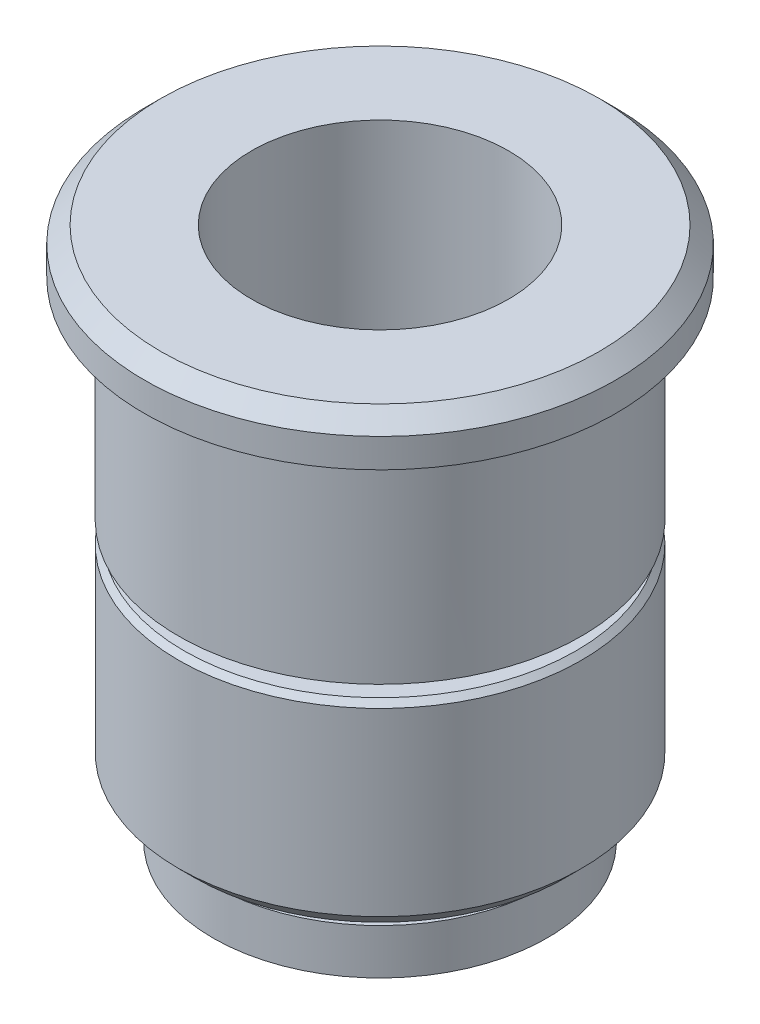
SolidWorks part; units mm, degrees
material "Brass"
ref_plane "Front" through (0, 0, 0) normal (0, 0, 1) x (1, 0, 0)
ref_plane "Top" through (0, 0, 0) normal (0, 1, 0) x (1, 0, 0)
ref_plane "Right" through (0, 0, 0) normal (1, 0, 0) x (0, 0, -1)
sketch "Sketch1" plane through (0, 0, 0) normal (0, 0, 1) x (1, 0, 0)
  line L0 (0, 0) -> (0, 6.23) construction
  line L1 (0, 0) -> (1.95, 0) construction
  line L2 (0, 6.23) -> (2.75, 6.23) construction
  line L3 (2.75, 6.23) -> (2.75, 5.7) construction
  line L4 (0, 0.71) -> (2.35, 0.71) construction
  line L5 (1.5, 6.23) -> (1.5, 0) construction
  line L6 (1.95, 0) -> (1.95, 0.53) construction
  line L7 (1.5, 0) -> (1.95, 0) construction
  line L8 (1.725, 0) -> (1.725, 6.23) construction
  line L9 (1.95, 0.53) -> (1.725, 0.53) construction
  line L10 (1.725, 0.53) -> (1.725, 0.71) construction
  line L11 (2.75, 5.7) -> (1.725, 5.7) construction
  line L12 (1.725, 5.7) -> (1.725, 5.61) construction
  line L13 (1.725, 5.61) -> (2.35, 5.61) construction
  line L14 (2.35, 5.61) -> (2.35, 3.25) construction
  line L15 (2.35, 3.25) -> (1.725, 3.25) construction
  line L16 (1.725, 3.25) -> (1.725, 3.07) construction
  line L17 (1.725, 3.07) -> (2.35, 3.07) construction
  line L18 (2.35, 3.07) -> (2.35, 0.71) construction
  line L19 (1.725, 0.71) -> (1.725, 0.53) construction
  point P13 (1.725, 0)
  point P15 (1.5, 5.73)
  dimension "BaseFlange" = 3.9
  dimension "FlangeDia" = 5.5
  dimension "Flange Thickness" = 0.53
  dimension "BodyDia" = 4.7
  dimension "ThreadDia" = 3
  dimension "D1" = 0.53
  dimension "D3" = 0.09
  dimension "D2" = 0.18
  dimension "D4" = 0.18
  dimension "Pitch" = 0.5
  dimension "knurled body ht" = 2.36
  dimension "Lg" = 5.7
sketch "Sketch3" plane through (0, 0, 0) normal (0, 0, 1) x (1, 0, 0)
  line L0 (0, 0) -> (1.95, 0)
  line L1 (1.95, 0) -> (1.95, 0.53)
  line L2 (1.95, 0.53) -> (1.725, 0.53)
  line L3 (1.725, 0.53) -> (1.725, 0.71)
  line L4 (1.725, 0.71) -> (2.35, 0.71)
  line L5 (2.35, 0.71) -> (2.35, 3.07)
  line L6 (2.35, 3.07) -> (1.725, 3.07)
  line L7 (1.725, 3.07) -> (1.725, 3.25)
  line L8 (1.725, 3.25) -> (2.35, 3.25)
  line L9 (2.35, 3.25) -> (2.35, 5.61)
  line L10 (2.35, 5.61) -> (1.725, 5.61)
  line L11 (1.725, 5.61) -> (1.725, 5.7)
  line L12 (1.725, 5.7) -> (2.75, 5.7)
  line L13 (2.75, 5.7) -> (2.75, 6.23)
  line L14 (2.75, 6.23) -> (0, 6.23)
  line L15 (0, 6.23) -> (0, 0)
revolve "Revolve1" add sketch "Sketch3" angle 360 about L0
sketch "Sketch5" plane through (0, 0, 0) normal (0, 0, 1) x (1, 0, 0)
  line L1 (0, 0) -> (1.5, 0)
  line L2 (0, 0) -> (0, 6.23)
  line L3 (0, 6.23) -> (1.5, 6.23)
  line L4 (1.5, 0) -> (1.5, 6.23)
revolve "Cut-Revolve1" cut sketch "Sketch5" angle 360 about L0
chamfer "Chamfer1" distance 0.0635 angle 45 2 edges at (0, 3.07, -2.35) (0, 5.61, -2.35)
chamfer "Chamfer2" distance 0.1925 angle 45 2 edges at (0, 6.23, -2.75) (0, 0.71, -2.35)
sketch "Sketch6" plane through (0, 6.23, 0) normal (0, 1, 0) x (1, 0, 0)
  circle A0 centre (0, 0) radius 1.5 construction
  circle A1 centre (0, 0) radius 1.5 construction
  circle A2 centre (0, 0) radius 1.5 construction
  circle A3 centre (0, 0) radius 1.5 construction
  circle A4 centre (0, 0) radius 1.5
curve "Helix/Spiral1" [suppressed] pitch 0.5 height 8.55 turns 17.1 parameters "Threa"=8.55, "Pitch"=0.5
sketch "Sketch13" plane through (0, 0, 0) normal (0, 0, 1) x (1, 0, 0)
  line L0 (-2.75, 5.7) -> (-2.75, 0) construction
  line L1 (-1.95, 0) -> (1.95, 0) construction
  line L2 (-2.75, 5.7) -> (2.75, 5.7) construction
  line L3 (-2.75, 6.0375) -> (-2.75, 5.7) construction
  line L4 (0, 0) -> (0, 6.23) construction
  line L5 (1.5, 6.23) -> (-1.5, 6.23) construction
  line L6 (0, 6.23) -> (1.5, 6.23) construction
  line L7 (-2.75, 5.7) -> (2.75, 5.7) construction
  line L8 (-2.75, 3.115) -> (2.75, 3.115) construction
  point P8 (1.5, 6.23)
  point P20 (0, 3.115)
sketch "Sketch14" plane through (0, 6.23, 0) normal (0, 1, 0) x (1, 0, 0)
  line L0 (0, 0) -> (1.0607, -1.0607) construction
  line L1 (0, 0) -> (0, -1.5) construction
  circle A0 centre (0, 0) radius 1.5 construction
  point P8 (1.0607, -1.0607)
  dimension "D1" = 45
sketch "Sketch7" [suppressed] plane through (0, 0, 0) normal (0, 0, 1) x (1, 0, 0)
  line L0 (-1.5, 6.23) -> (-1.5, 6.6675)
  line L1 (-1.5, 6.6675) -> (-1.1752, 6.48)
  line L2 (-1.1752, 6.48) -> (-1.1752, 6.4175)
  line L3 (-1.1752, 6.4175) -> (-1.5, 6.23)
  line L4 (-1.1752, 6.4488) -> (-1.5, 6.4488) construction
  line L5 (-1.3376, 6.5738) -> (-1.3376, 6.3238) construction
  dimension "D1" = 0.0625
  dimension "D2" = 0.25
  dimension "D3" = 60
sweep "Sweep1" [suppressed] add profiles "Sketch7" path "Helix/Spiral1"
sketch "Sketch9" [suppressed] plane through (0, 6.23, 0) normal (0, 1, 0) x (1, 0, 0)
  circle A0 centre (0, 0) radius 1.5 construction
  circle A1 centre (0, 0) radius 1.5
extrude "Cut-Extrude1" [suppressed] cut sketch "Sketch9" along normal blind 25.4 draft 45 and the other way blind 2.54 draft 45 draft outward yes
sketch "Sketch10" [suppressed] plane through (0, 0, 0) normal (0, -1, 0) x (1, 0, 0)
  circle A1 centre (0, 0) radius 1.5
  dimension "D1" = 3
extrude "Cut-Extrude2" [suppressed] cut sketch "Sketch10" along normal blind 25.908 draft 45 and the other way blind 6.35 draft 45 draft outward yes
sketch "Sketch11" [suppressed] plane through (0, 5.61, 0) normal (0, 1, 0) x (1, 0, 0)
  line L0 (0, 0) -> (0, -2.35) construction
  line L1 (0, 0) -> (0.1435, -2.3456) construction
  line L2 (0, 0) -> (-0.1435, -2.3456) construction
  circle A0 centre (0, 0) radius 2.35 construction
  circle A1 centre (0, -2.35) radius 0.1435
  dimension "D1" = 3.5
  dimension "D2" = 3.5
sketch "Sketch12" plane through (0, 5.61, 0) normal (0, 1, 0) x (1, 0, 0)
  circle A0 centre (0, 0) radius 2.35 construction
  circle A1 centre (0, 0) radius 2.35
curve "Helix/Spiral2" [suppressed] pitch 28.51 height 2.365 turns 0.083
sweep "Cut-Sweep1" [suppressed] cut profiles "Sketch11" path "Helix/Spiral2"
pattern_circular "CirPattern1" [suppressed] count 30 over 360 of bodies 117
ref_plane "Plane1" [suppressed] through (0, 3.16, 0) normal (0, -1, 0) x (-1, 0, 0)
mirror "Mirror1" [suppressed] about plane through (0, 3.16, 0) normal (0, -1, 0)
ref_plane "Contact Plane 1" [suppressed] through (0, 6.23, 0) normal (0, 1, 0) x (1, 0, 0)
ref_plane "Contact Plane 2" [suppressed] through (0, 0, 0) normal (0, 1, 0) x (1, 0, 0)
ref_plane "Contact Plane 3" [suppressed] through (-2.75, 0, 0) normal (1, 0, 0) x (0, 0, -1)
ref_plane "Contact Plane 4" [suppressed] through (2.75, 0, 0) normal (1, 0, 0) x (0, 0, -1)
ref_plane "Contact Plane 5" [suppressed] through (0, 3.115, 0) normal (0, 1, 0) x (1, 0, 0)
ref_plane "Contact Plane 6" [suppressed] through (0, 5.7, 0) normal (0, -1, 0) x (-1, 0, 0)
ref_axis "Center Axis 1" [suppressed] through (0, 7.0965, 0) along (0, -1, 0)
equation "\"D1@Sketch1\"=\"Flange Thickness@Sketch1\""
equation "\"D3@Sketch1\"=\"D2@Sketch1\"*.50"
equation "\"D4@Sketch1\"=\"D2@Sketch1\""
equation "\"Threa@Helix/Spiral1\" = \"Lg@Sketch1\" +  ( \"Lg@Sketch1\" / 2 ) "
equation "\"Pitch@Helix/Spiral1\"=\"Pitch@Sketch1\""
equation "\"D1@Sketch7\"=\"Pitch@Sketch1\"*.125"
equation "\"D2@Sketch7\"=\"Pitch@Sketch1\"*.50"
equation "\"D1@Sketch10\"=\"ThreadDia@Sketch1\""
equation "\"D1@Chamfer2\"=\"FlangeDia@Sketch1\"*.035"
equation "\"D3@Helix/Spiral2\"=\"knurled body ht@Sketch1\"+.005"
equation "\"D2@Sketch1\"=\"ThreadDia@Sketch1\"*.06"
